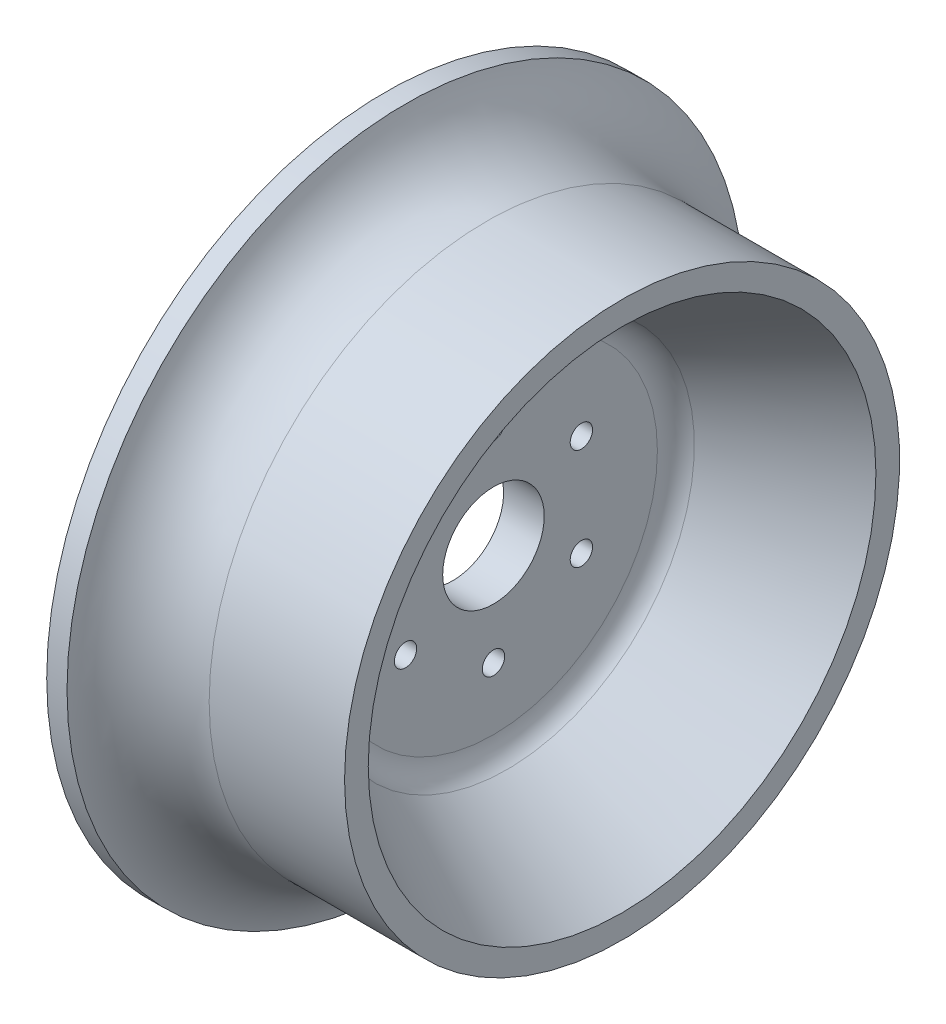
SolidWorks part; units mm, degrees
material "POM-C"
ref_plane "Płaszczyzna przednia" through (0, 0, 0) normal (0, 0, 1) x (1, 0, 0)
ref_plane "Płaszczyzna górna" through (0, 0, 0) normal (0, 1, 0) x (1, 0, 0)
ref_plane "Płaszczyzna prawa" through (0, 0, 0) normal (1, 0, 0) x (0, 0, -1)
sketch "Szkic1" plane through (0, 0, 0) normal (0, 0, 1) x (1, 0, 0)
  line L0 (0, 0) -> (61.0087, 0) construction
  line L1 (0, 100) -> (6, 100)
  line L2 (0, 100) -> (0, 15)
  line L3 (30, 82) -> (70, 82)
  line L4 (0, 127) -> (64.4986, 127) construction
  line L5 (70, 82) -> (70, 15)
  line L8 (70, 15) -> (0, 15)
  arc A0 (6, 100) -> (30, 82) centre (30, 107) ccw
  dimension "D3" = 25
  dimension "D4" = 200
  dimension "D5" = 30
  dimension "D1" = 127
  dimension "D2" = 45
  dimension "D7" = 70
  dimension "D9" = 30
  dimension "D12" = 164
  dimension "D13" = 65
revolve "Obrót1" add sketch "Szkic1" angle 360 about L0
sketch "Szkic2" plane through (0, 0, 0) normal (-1, 0, 0) x (0, 0, 1)
  line L1 (-4, 18.3) -> (4, 18.3)
  line L2 (-4, 18.3) -> (-4, 0)
  line L3 (-4, 0) -> (4, 0)
  line L4 (4, 18.3) -> (4, 0)
  circle A0 centre (0, 0) radius 15 construction
  dimension "D2" = 3.3
  dimension "D1" = 8
extrude "Wytnij-wyciągnięcie1" [suppressed] cut sketch "Szkic2" against normal up to next
sketch "Szkic3" plane through (0, 0, 0) normal (0, 0, 1) x (1, 0, 0)
  line L0 (0, 0) -> (70, 0) construction
  line L1 (70, -82) -> (70, 82) construction
  line L3 (0, 100) -> (0, -100) construction
  line L4 (20, 0) -> (20, 61.1742)
  line L6 (0, 80.5425) -> (0, 0)
  line L7 (0, 0) -> (20, 0)
  line L8 (32, 0) -> (32, 48.4419)
  line L9 (36, 55.3701) -> (70, 75)
  line L10 (70, 75) -> (70, 0)
  line L11 (70, 0) -> (32, 0)
  arc A1 (20, 61.1742) -> (14, 70.3394) centre (10, 61.1742) ccw
  arc A2 (14, 70.3394) -> (0, 80.5425) centre (30, 107) cw
  arc A3 (6, 100) -> (30, 82) centre (30, 107) ccw construction
  arc A4 (32, 48.4419) -> (36, 55.3701) centre (40, 48.4419) cw
  dimension "D2" = 12
  dimension "D4" = 40
  dimension "D1" = 10
  dimension "D6" = 8
  dimension "D3" = 20
  dimension "D5" = 38
  dimension "D7" = 60
  dimension "D8" = 150
revolve "Wycięcie-obrót1" cut sketch "Szkic3" angle 360 about L0
hole_wizard "Otwór pod śrubę M61" positions "Szkic4" profile "Szkic5" hole size "M6" standard "DIN" end condition up to next
sketch "Szkic4" plane through (32, 0, 0) normal (-1, 0, 0) x (0, 0, 1)
  line L0 (0, 0) -> (0, 30) construction
  point P0 (0, 30)
  dimension "D1" = 30
sketch "Szkic5" plane through (32, 30, 0) normal (0, 1, 0) x (0, 0, -1)
  line L0 (0, 0) -> (0, 12.001)
  line L1 (0, 12.001) -> (3.3, 12.001)
  line L2 (3.3, 12.001) -> (3.3, 0)
  line L5 (3.3, 0) -> (0, 0)
  line L11 (0, -6.35) -> (0, 107.95) construction
  dimension "Średnica otworu na wylot" = 6.6
  dimension "Głębokość otworu na wylot" = 12.001
pattern_circular "Szyk kołowy1" count 6 over 360 about axis through (0, 0, 0) along (-1, 0, 0) of "Otwór pod śrubę M61"
